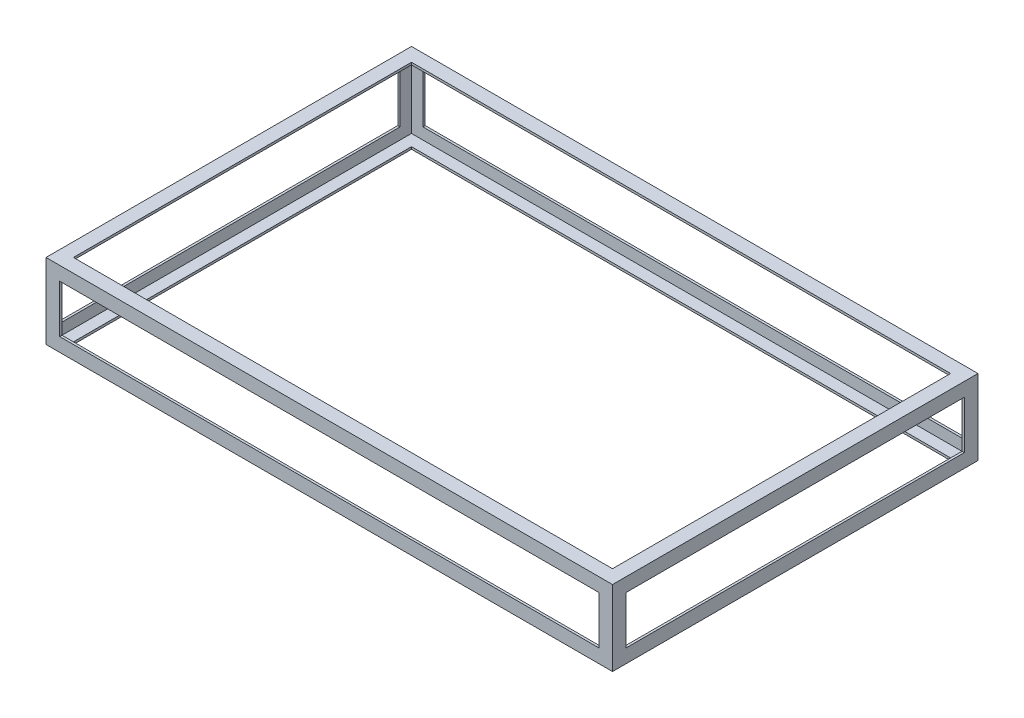
SolidWorks part; units mm, degrees
material "6061 Alloy"
ref_plane "Front Plane" through (0, 0, 0) normal (0, 0, 1) x (1, 0, 0)
ref_plane "Top Plane" through (0, 0, 0) normal (0, 1, 0) x (1, 0, 0)
ref_plane "Right Plane" through (0, 0, 0) normal (1, 0, 0) x (0, 0, -1)
other "Center of Mass"
sketch "Sketch2" plane through (0, 0, 0) normal (1, 0, 0) x (0, 0, -1)
  line L0 (-504.825, -346.075) -> (-504.825, -422.275)
  line L1 (504.825, -422.275) -> (-504.825, -422.275) construction
  line L2 (504.825, -422.275) -> (504.825, 422.275) construction
  line L3 (504.825, 422.275) -> (-504.825, 422.275) construction
  line L4 (-504.825, -422.275) -> (-504.825, 422.275) construction
  line L5 (504.825, -422.275) -> (-504.825, 422.275) construction
  line L6 (504.825, 422.275) -> (-504.825, -422.275) construction
  line L7 (-504.825, -422.275) -> (-428.625, -422.275)
  line L8 (-428.625, -422.275) -> (-428.625, -417.195)
  line L9 (-428.625, -417.195) -> (-498.7519, -417.195)
  line L10 (-498.7519, -417.195) -> (-498.7519, -346.075)
  line L11 (-498.7519, -346.075) -> (-504.825, -346.075)
  line L12 (0, 0) -> (0, -148.4726) construction
  line L13 (0, 0) -> (158.633, 0) construction
  line L14 (498.7519, -417.195) -> (498.7519, -346.075)
  line L15 (428.625, -417.195) -> (498.7519, -417.195)
  line L16 (428.625, -422.275) -> (428.625, -417.195)
  line L17 (504.825, -422.275) -> (428.625, -422.275)
  line L18 (504.825, -346.075) -> (504.825, -422.275)
  line L19 (498.7519, -346.075) -> (504.825, -346.075)
  line L20 (428.625, 417.195) -> (498.7519, 417.195)
  line L21 (428.625, 422.275) -> (428.625, 417.195)
  line L22 (504.825, 422.275) -> (428.625, 422.275)
  line L23 (504.825, 346.075) -> (504.825, 422.275)
  line L24 (498.7519, 346.075) -> (504.825, 346.075)
  line L25 (498.7519, 417.195) -> (498.7519, 346.075)
  line L26 (-498.7519, 417.195) -> (-498.7519, 346.075)
  line L27 (-428.625, 417.195) -> (-498.7519, 417.195)
  line L28 (-428.625, 422.275) -> (-428.625, 417.195)
  line L29 (-504.825, 422.275) -> (-428.625, 422.275)
  line L30 (-504.825, 346.075) -> (-504.825, 422.275)
  line L31 (-498.7519, 346.075) -> (-504.825, 346.075)
  point P0 (0, 0)
  dimension "D1" = 1009.65
  dimension "D2" = 844.55
  dimension "D3" = 76.2
  dimension "D4" = 5.08
extrude "OAL Lenth" [suppressed] add sketch "Sketch2" along normal blind 1574.8
sketch "Sketch3" [suppressed] plane through (0, 0, 0) normal (0, 0, 1) x (1, 0, 0)
  line L0 (0, -422.275) -> (0, -346.075)
  line L1 (1574.8, -346.075) -> (0, -346.075) construction
  line L2 (0, -346.075) -> (0, -422.275) construction
  line L3 (0, -346.075) -> (5.08, -346.075)
  line L4 (5.08, -346.075) -> (5.08, -417.195)
  line L5 (5.08, -417.195) -> (76.2, -417.195)
  line L6 (76.2, -417.195) -> (76.2, -422.275)
  line L7 (1574.8, -422.275) -> (0, -422.275) construction
  line L8 (76.2, -422.275) -> (0, -422.275)
  line L9 (0, 0) -> (697.1877, 0) construction
  line L10 (787.4, 346.075) -> (787.4, -346.075) construction
  line L11 (1574.8, 346.075) -> (0, 346.075) construction
  line L12 (76.2, 422.275) -> (0, 422.275)
  line L13 (76.2, 417.195) -> (76.2, 422.275)
  line L14 (5.08, 417.195) -> (76.2, 417.195)
  line L15 (5.08, 346.075) -> (5.08, 417.195)
  line L16 (0, 346.075) -> (5.08, 346.075)
  line L17 (0, 422.275) -> (0, 346.075)
  line L18 (1574.8, 422.275) -> (1574.8, 346.075)
  line L19 (1574.8, 346.075) -> (1569.72, 346.075)
  line L20 (1569.72, 346.075) -> (1569.72, 417.195)
  line L21 (1569.72, 417.195) -> (1498.6, 417.195)
  line L22 (1498.6, 417.195) -> (1498.6, 422.275)
  line L23 (1498.6, 422.275) -> (1574.8, 422.275)
  line L24 (1498.6, -422.275) -> (1574.8, -422.275)
  line L25 (1498.6, -417.195) -> (1498.6, -422.275)
  line L26 (1569.72, -417.195) -> (1498.6, -417.195)
  line L27 (1569.72, -346.075) -> (1569.72, -417.195)
  line L28 (1574.8, -346.075) -> (1569.72, -346.075)
  line L29 (1574.8, -422.275) -> (1574.8, -346.075)
  dimension "D1" = 5.08
extrude "OAL Width" [suppressed] add sketch "Sketch3" along normal up to surface and the other way up to surface
sketch "Sketch4" [suppressed] plane through (0, 422.275, 0) normal (0, 1, 0) x (1, 0, 0)
  line L0 (0, 504.825) -> (0, 428.625)
  line L1 (0, -428.625) -> (0, -504.825) construction
  line L2 (0, 428.625) -> (5.08, 428.625)
  line L3 (5.08, 428.625) -> (5.08, 499.745)
  line L4 (5.08, 499.745) -> (76.2, 499.745)
  line L5 (76.2, 499.745) -> (76.2, 504.825)
  line L6 (0, 504.825) -> (1574.8, 504.825) construction
  line L7 (76.2, 504.825) -> (0, 504.825)
  line L8 (0, 0) -> (1574.8, 0) construction
  line L9 (1574.8, -428.625) -> (1574.8, -504.825) construction
  line L10 (787.4, 0) -> (787.4, 504.825) construction
  line L11 (76.2, -504.825) -> (0, -504.825)
  line L12 (76.2, -499.745) -> (76.2, -504.825)
  line L13 (5.08, -499.745) -> (76.2, -499.745)
  line L14 (5.08, -428.625) -> (5.08, -499.745)
  line L15 (0, -428.625) -> (5.08, -428.625)
  line L16 (0, -504.825) -> (0, -428.625)
  line L17 (1574.8, -504.825) -> (1574.8, -428.625)
  line L18 (1574.8, -428.625) -> (1569.72, -428.625)
  line L19 (1569.72, -428.625) -> (1569.72, -499.745)
  line L20 (1569.72, -499.745) -> (1498.6, -499.745)
  line L21 (1498.6, -499.745) -> (1498.6, -504.825)
  line L22 (1498.6, -504.825) -> (1574.8, -504.825)
  line L23 (1498.6, 504.825) -> (1574.8, 504.825)
  line L24 (1498.6, 499.745) -> (1498.6, 504.825)
  line L25 (1569.72, 499.745) -> (1498.6, 499.745)
  line L26 (1569.72, 428.625) -> (1569.72, 499.745)
  line L27 (1574.8, 428.625) -> (1569.72, 428.625)
  line L28 (1574.8, 504.825) -> (1574.8, 428.625)
  dimension "D1" = 5.08
  dimension "D2" = 76.2
extrude "OAL Height" [suppressed] add sketch "Sketch4" against normal through all
sketch "Sketch5" plane through (0, 0, 0) normal (1, 0, 0) x (0, 0, -1)
  line L0 (0, 304.8) -> (0, -304.8) construction
  line L1 (-508, -304.8) -> (508, -304.8) construction
  line L2 (-508, -304.8) -> (-508, -266.7)
  line L3 (-508, -304.8) -> (-469.9, -304.8)
  line L4 (-469.9, -304.8) -> (-469.9, -298.45)
  line L5 (-469.9, -298.45) -> (-501.65, -298.45)
  line L6 (-501.65, -298.45) -> (-501.65, -266.7)
  line L7 (-501.65, -266.7) -> (-508, -266.7)
  line L8 (501.65, -266.7) -> (508, -266.7)
  line L9 (501.65, -298.45) -> (501.65, -266.7)
  line L10 (469.9, -298.45) -> (501.65, -298.45)
  line L11 (469.9, -304.8) -> (469.9, -298.45)
  line L12 (508, -304.8) -> (469.9, -304.8)
  line L13 (508, -304.8) -> (508, -266.7)
  line L14 (0, -200.025) -> (-176.3903, -200.025) construction
  line L15 (-508, -95.25) -> (508, -95.25) construction
  line L16 (508, -95.25) -> (508, -133.35)
  line L17 (508, -95.25) -> (469.9, -95.25)
  line L18 (469.9, -95.25) -> (469.9, -101.6)
  line L19 (469.9, -101.6) -> (501.65, -101.6)
  line L20 (501.65, -101.6) -> (501.65, -133.35)
  line L21 (501.65, -133.35) -> (508, -133.35)
  line L22 (-501.65, -133.35) -> (-508, -133.35)
  line L23 (-501.65, -101.6) -> (-501.65, -133.35)
  line L24 (-469.9, -101.6) -> (-501.65, -101.6)
  line L25 (-469.9, -95.25) -> (-469.9, -101.6)
  line L26 (-508, -95.25) -> (-469.9, -95.25)
  line L27 (-508, -95.25) -> (-508, -133.35)
  point P4 (0, 0)
  point P8 (0, -304.8)
  point P32 (0, -95.25)
  dimension "D1" = 1016
  dimension "D2" = 609.6
  dimension "D3" = 38.1
  dimension "D4" = 6.35
  dimension "D5" = 104.775
extrude "X Angle Lenth" add sketch "Sketch5" along normal blind 1574.8 separate body
sketch "Sketch6" plane through (0, -304.8, 0) normal (0, -1, 0) x (1, 0, 0)
  line L0 (0, 0) -> (1574.8, 0) construction
  line L1 (1574.8, -508) -> (1574.8, 508) construction
  line L2 (1574.8, -508) -> (1536.7, -508)
  line L3 (1574.8, -508) -> (1574.8, -469.9)
  line L4 (1574.8, -469.9) -> (1568.45, -469.9)
  line L5 (1568.45, -469.9) -> (1568.45, -501.65)
  line L6 (1568.45, -501.65) -> (1536.7, -501.65)
  line L7 (1536.7, -501.65) -> (1536.7, -508)
  line L8 (1536.7, 501.65) -> (1536.7, 508)
  line L9 (1568.45, 501.65) -> (1536.7, 501.65)
  line L10 (1568.45, 469.9) -> (1568.45, 501.65)
  line L11 (1574.8, 469.9) -> (1568.45, 469.9)
  line L12 (1574.8, 508) -> (1574.8, 469.9)
  line L13 (1574.8, 508) -> (1536.7, 508)
  line L15 (787.4, 0) -> (787.4, 197.6325) construction
  line L16 (0, -508) -> (0, 508) construction
  line L17 (0, 508) -> (38.1, 508)
  line L18 (0, 508) -> (0, 469.9)
  line L19 (0, 469.9) -> (6.35, 469.9)
  line L20 (6.35, 469.9) -> (6.35, 501.65)
  line L21 (6.35, 501.65) -> (38.1, 501.65)
  line L22 (38.1, 501.65) -> (38.1, 508)
  line L23 (38.1, -501.65) -> (38.1, -508)
  line L24 (6.35, -501.65) -> (38.1, -501.65)
  line L25 (6.35, -469.9) -> (6.35, -501.65)
  line L26 (0, -469.9) -> (6.35, -469.9)
  line L27 (0, -508) -> (0, -469.9)
  line L28 (0, -508) -> (38.1, -508)
  point P3 (787.4, 0)
  point P6 (1574.8, 0)
  point P32 (0, 0)
  dimension "D1" = 38.1
  dimension "D2" = 6.35
  dimension "D3" = 1016
  dimension "D4" = 1574.8
extrude "Y Angle Lenth" add sketch "Sketch6" against normal blind 209.55
sketch "Sketch12" plane through (0, 0, 0) normal (-1, 0, 0) x (0, 0, 1)
  line L0 (0, -304.8) -> (0, 304.8) construction
  line L1 (0, -304.8) -> (-469.9, -304.8) construction
  line L2 (-279.4, 304.8) -> (279.4, 304.8) construction
  line L3 (279.4, 304.8) -> (508, -95.25)
  line L4 (508, -95.25) -> (322.1581, -95.25)
  line L5 (469.9, -95.25) -> (508, -95.25) construction
  line L6 (508, -95.25) -> (508, -304.8) construction
  point P9 (0, 304.8)
  dimension "D1" = 609.6
  dimension "D2" = 558.8
ref_plane "Plane2" through (0, -95.25, 508) normal (0, -0.8682, 0.4961) x (-1, 0, 0)
sketch "Sketch13" plane through (0, -95.25, 508) normal (0, -0.8682, 0.4961) x (-1, 0, 0)
  line L0 (0, 0) -> (0, 38.1)
  line L1 (0, 485.1743) -> (0, 0) construction
  line L2 (0, 38.1) -> (-3.175, 38.1)
  line L3 (-3.175, 38.1) -> (-3.175, 3.175)
  line L4 (-3.175, 3.175) -> (-38.1, 3.175)
  line L5 (-38.1, 3.175) -> (-38.1, 0)
  line L6 (-1574.8, 0) -> (0, 0) construction
  line L7 (-38.1, 0) -> (0, 0)
  line L8 (0, 0) -> (-558.8, 0) construction
  line L9 (-279.4, 0) -> (-279.4, -79.7814) construction
  line L10 (-520.7, 0) -> (-558.8, 0)
  line L11 (-520.7, 3.175) -> (-520.7, 0)
  line L12 (-555.625, 3.175) -> (-520.7, 3.175)
  line L13 (-555.625, 38.1) -> (-555.625, 3.175)
  line L14 (-558.8, 38.1) -> (-555.625, 38.1)
  line L15 (-558.8, 0) -> (-558.8, 38.1)
  line L16 (-1574.8, 0) -> (0, 0) construction
  dimension "D1" = 3.175
  dimension "D2" = 38.1
  dimension "D3" = 558.8
extrude "Rear Diagonal Angle" [suppressed] add sketch "Sketch13" against normal up to vertex up to point (0, 304.8, 279.4)
sketch "Sketch14" [suppressed] plane through (0, 0, 0) normal (0, 0, 1) x (1, 0, 0)
  line L1 (0, 304.8) -> (0, -95.25) construction
  line L2 (0, -95.25) -> (558.8, -95.25) construction
  line L3 (279.4, -95.25) -> (279.4, 65.0322) construction
  line L4 (553.72, 266.7) -> (558.8, 266.7)
  line L5 (558.8, 266.7) -> (558.8, 304.8)
  line L6 (558.8, 304.8) -> (520.7, 304.8)
  line L12 (520.7, 304.8) -> (520.7, 299.72)
  line L13 (520.7, 299.72) -> (553.72, 299.72)
  line L26 (5.08, 299.72) -> (5.08, 266.7)
  line L27 (38.1, 299.72) -> (5.08, 299.72)
  line L28 (38.1, 304.8) -> (38.1, 299.72)
  line L29 (0, 304.8) -> (38.1, 304.8)
  line L30 (0, 266.7) -> (0, 304.8)
  line L31 (5.08, 266.7) -> (0, 266.7)
  line L32 (553.72, 299.72) -> (553.72, 266.7)
  dimension "D1" = 38.1
  dimension "D2" = 5.08
extrude "Rear Top Angle" [suppressed] add sketch "Sketch14" along normal up to next
sketch "Sketch7" plane through (0, -304.8, 0) normal (0, -1, 0) x (1, 0, 0)
  line L0 (609.6, 0) -> (0, 0) construction
  line L1 (0, 504.825) -> (0, -504.825) construction
  line L2 (0, 504.825) -> (50.8, 504.825)
  line L3 (0, 504.825) -> (0, 454.025)
  line L4 (0, 454.025) -> (3.175, 454.025)
  line L5 (3.175, 454.025) -> (3.175, 501.65)
  line L6 (3.175, 501.65) -> (50.8, 501.65)
  line L7 (50.8, 501.65) -> (50.8, 504.825)
  line L8 (50.8, -501.65) -> (50.8, -504.825)
  line L9 (3.175, -501.65) -> (50.8, -501.65)
  line L10 (3.175, -454.025) -> (3.175, -501.65)
  line L11 (0, -454.025) -> (3.175, -454.025)
  line L12 (0, -504.825) -> (0, -454.025)
  line L13 (0, -504.825) -> (50.8, -504.825)
  point P3 (304.8, 0)
  point P6 (0, 0)
extrude "Rear Vertical Angle" [suppressed] add sketch "Sketch7" against normal blind 609.6
sketch "Sketch8" plane through (0, 0, 0) normal (-1, 0, 0) x (0, 0, 1)
  line L0 (0, -304.8) -> (0, 304.8) construction
  line L2 (279.4, 304.8) -> (279.4, 266.7)
  line L3 (279.4, 304.8) -> (241.3, 304.8)
  line L4 (241.3, 304.8) -> (241.3, 301.625)
  line L5 (241.3, 301.625) -> (276.225, 301.625)
  line L6 (276.225, 301.625) -> (276.225, 266.7)
  line L7 (276.225, 266.7) -> (279.4, 266.7)
  point P3 (0, 0)
  point P6 (0, 304.8)
  dimension "D1" = 38.1
extrude "Rear Top Horizontal Angle" [suppressed] add sketch "Sketch8" against normal up to surface (558.8 mm away)
sketch "Sketch15" plane through (0, 0, 0) normal (0, 0, 1) x (1, 0, 0)
  line L0 (0, -266.7) -> (0, -304.8)
  line L1 (0, -95.25) -> (1574.8, -95.25) construction
  line L2 (787.4, -95.25) -> (787.4, 43.9233) construction
  line L3 (1568.45, -266.7) -> (1574.8, -266.7)
  line L4 (1568.45, -298.45) -> (1568.45, -266.7)
  line L5 (1536.7, -298.45) -> (1568.45, -298.45)
  line L6 (1536.7, -304.8) -> (1536.7, -298.45)
  line L7 (0, -304.8) -> (38.1, -304.8)
  line L8 (38.1, -304.8) -> (38.1, -298.45)
  line L9 (38.1, -298.45) -> (6.35, -298.45)
  line L10 (6.35, -298.45) -> (6.35, -266.7)
  line L11 (6.35, -266.7) -> (0, -266.7)
  line L12 (1574.8, -304.8) -> (1536.7, -304.8)
  line L13 (1574.8, -266.7) -> (1574.8, -304.8)
  line L20 (787.4, -95.25) -> (787.4, -304.8) construction
  line L21 (1574.8, -304.8) -> (0, -304.8) construction
  line L24 (787.4, -200.025) -> (896.4031, -200.025) construction
  line L27 (1574.8, -133.35) -> (1574.8, -95.25)
  line L28 (1574.8, -95.25) -> (1536.7, -95.25)
  line L29 (1536.7, -95.25) -> (1536.7, -101.6)
  line L30 (1536.7, -101.6) -> (1568.45, -101.6)
  line L31 (1568.45, -101.6) -> (1568.45, -133.35)
  line L32 (1568.45, -133.35) -> (1574.8, -133.35)
  line L33 (18.8814, -200.025) -> (113.1502, -200.025) construction
  line L35 (6.35, -133.35) -> (0, -133.35)
  line L36 (6.35, -101.6) -> (6.35, -133.35)
  line L37 (38.1, -101.6) -> (6.35, -101.6)
  line L38 (38.1, -95.25) -> (38.1, -101.6)
  line L39 (0, -95.25) -> (38.1, -95.25)
  line L40 (0, -133.35) -> (0, -95.25)
  dimension "D1" = 38.1
  dimension "D2" = 6.35
extrude "Z Angle Lenth" add sketch "Sketch15" against normal up to surface and the other way up to surface up to face at (787.4, -200.025, -508) other way up to face at (787.4, -200.025, 508)
